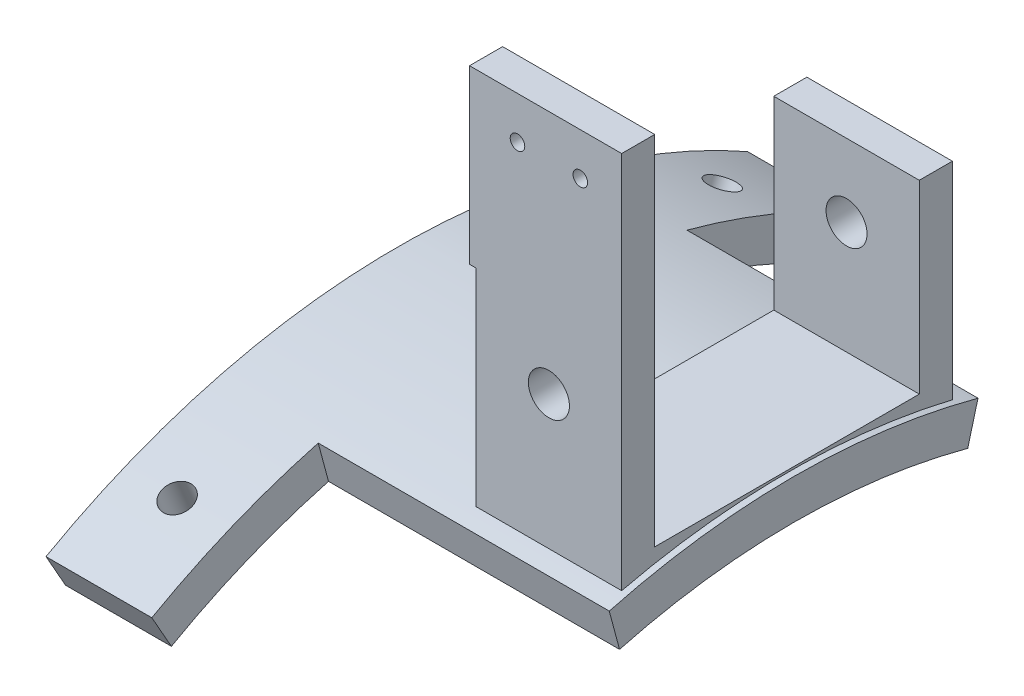
SolidWorks part; units mm, degrees
ref_plane "Front Plane" through (0, 0, 0) normal (0, 0, 1) x (1, 0, 0)
ref_plane "Top Plane" through (0, 0, 0) normal (0, 1, 0) x (1, 0, 0)
ref_plane "Right Plane" through (0, 0, 0) normal (1, 0, 0) x (0, 0, -1)
sketch "Row Sketch" plane through (0, 0, 0) normal (0, 0, 1) x (1, 0, 0)
  line L0 (-3000, 0) -> (3000, 0) construction
  line L1 (-904, 101.7) -> (-888, 101.7)
  line L2 (-888, 101.7) -> (-888, 107.7)
  line L3 (-888, 107.7) -> (-904, 107.7)
  line L4 (-904, 107.7) -> (-904, 101.7)
revolve "Row" add sketch "Row Sketch" angle 59 mid plane about L0
ref_axis "Engine Axis" through (-841, 0, 0) along (-1, 0, 0)
sketch "Heel Sketch" plane through (0, 0, 0) normal (0, 0, 1) x (1, 0, 0)
  line L0 (-3000, 0) -> (3000, 0) construction
  line L1 (-888, 101.7) -> (-844, 101.7)
  line L2 (-844, 101.7) -> (-844, 107.7)
  line L3 (-844, 107.7) -> (-888, 107.7)
  line L4 (-888, 107.7) -> (-888, 101.7)
revolve "Heel" add sketch "Heel Sketch" angle 30 mid plane about L0
sketch "Lug Block Sketch" plane through (0, 0, 0) normal (0, 0, 1) x (1, 0, 0)
  line L0 (-867, 103) -> (-845, 103)
  line L1 (-845, 103) -> (-845, 136)
  line L2 (-845, 136) -> (-867, 136)
  line L3 (-867, 136) -> (-867, 103)
extrude "Lug Block" add sketch "Lug Block Sketch" along normal mid plane 50
sketch "Slot Sketch" plane through (0, 0, 0) normal (0, 0, 1) x (1, 0, 0)
  line L0 (-872, 108) -> (-840, 108)
  line L1 (-840, 108) -> (-840, 141)
  line L2 (-840, 141) -> (-872, 141)
  line L3 (-872, 141) -> (-872, 108)
extrude "Slot" cut sketch "Slot Sketch" against normal mid plane 40
sketch "Pin Hole Sketch" plane through (0, 0, 0) normal (0, 0, 1) x (1, 0, 0)
  circle A0 centre (-856, 125) radius 3.1
extrude "Pin Hole" cut sketch "Pin Hole Sketch" against normal mid plane 60
ref_plane "Tab Plane" through (0, 0, 20) normal (0, 0, 1) x (1, 0, 0)
sketch "Tab Sketch" plane through (0, 0, 20) normal (0, 0, 1) x (1, 0, 0)
  line L0 (-868, 136) -> (-845, 136)
  line L1 (-845, 136) -> (-845, 162)
  line L2 (-845, 162) -> (-868, 162)
  line L3 (-868, 162) -> (-868, 136)
extrude "Tab" add sketch "Tab Sketch" along normal blind 5
sketch "Switch Holes Sketch" plane through (0, 0, 0) normal (0, 0, 1) x (1, 0, 0)
  circle A0 centre (-860.75, 155.6) radius 1.1
  circle A1 centre (-851.25, 155.6) radius 1.1
extrude "Switch Holes" cut sketch "Switch Holes Sketch" against normal mid plane 60
ref_plane "Screw Hole -1 Plane" through (0, 0, 0) normal (0, -0.9239, 0.3827) x (-1, 0, 0)
sketch "Screw Hole -1 Sketch" plane through (0, 0, 0) normal (0, -0.9239, 0.3827) x (-1, 0, 0)
  circle A0 centre (896, 0) radius 2.25
extrude "Screw Hole -1" cut sketch "Screw Hole -1 Sketch" against normal blind 200
ref_plane "Screw Hole 1 Plane" through (0, 0, 0) normal (0, -0.9239, -0.3827) x (-1, 0, 0)
sketch "Screw Hole 1 Sketch" plane through (0, 0, 0) normal (0, -0.9239, -0.3827) x (-1, 0, 0)
  circle A0 centre (896, 0) radius 2.25
extrude "Screw Hole 1" cut sketch "Screw Hole 1 Sketch" against normal blind 200
